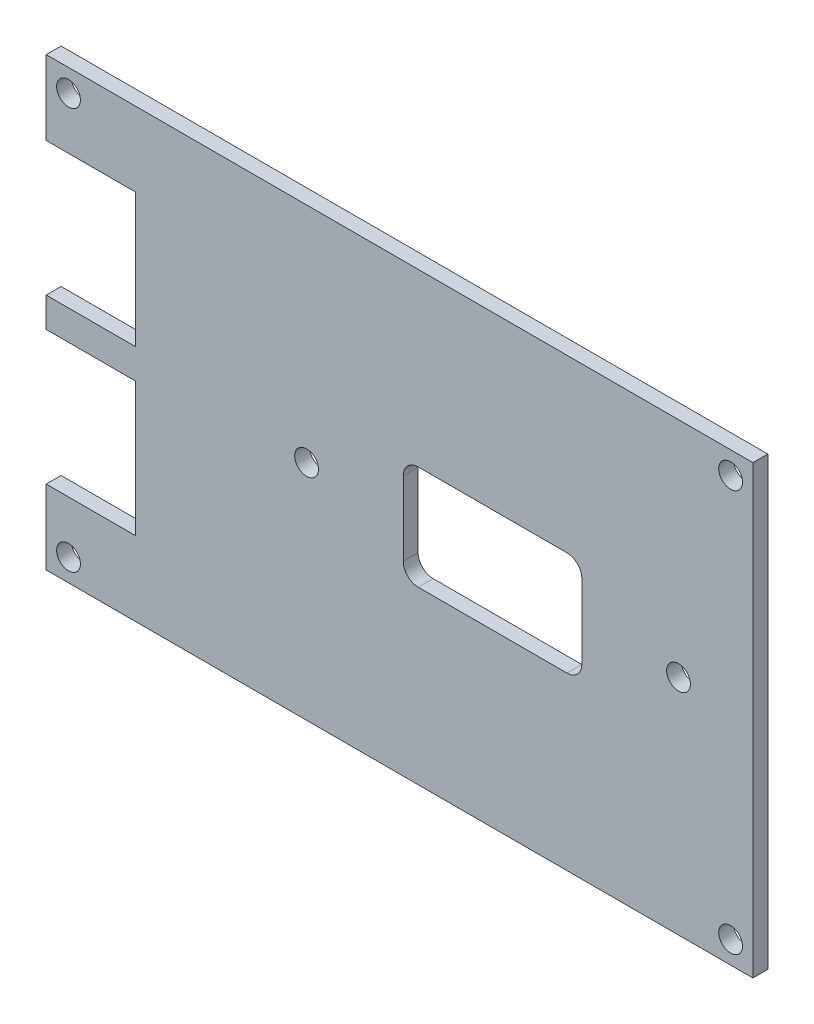
SolidWorks part; units mm, degrees
ref_plane "Front Plane" through (0, 0, 0) normal (0, 0, 1) x (1, 0, 0)
ref_plane "Top Plane" through (0, 0, 0) normal (0, 1, 0) x (1, 0, 0)
ref_plane "Right Plane" through (0, 0, 0) normal (1, 0, 0) x (0, 0, -1)
sketch "Sketch1" plane through (0, 0, 0) normal (0, 0, 1) x (1, 0, 0)
  line L0 (-4.5636, -11.1185) -> (20.4364, -11.1185) construction
  line L1 (-39.5636, 18.8815) -> (55.4364, 18.8815)
  line L2 (-39.5636, 18.8815) -> (-39.5636, 8.8815)
  line L3 (-39.5636, -41.1185) -> (55.4364, -41.1185)
  line L4 (55.4364, 18.8815) -> (55.4364, -41.1185)
  line L5 (20.4364, -4.1185) -> (20.4364, -11.1185) construction
  line L6 (10.4364, -4.1185) -> (30.4364, -4.1185)
  line L7 (8.4364, -6.1185) -> (8.4364, -16.1185)
  line L8 (10.4364, -18.1185) -> (30.4364, -18.1185)
  line L9 (32.4364, -6.1185) -> (32.4364, -16.1185)
  line L10 (20.4364, -18.1185) -> (20.4364, -11.1185) construction
  line L11 (20.4364, -11.1185) -> (45.4364, -11.1185) construction
  line L12 (-39.5636, -9.1185) -> (-39.5636, -13.1185)
  line L13 (-39.5636, 8.8815) -> (-27.5636, 8.8815)
  line L15 (-39.5636, -9.1185) -> (-27.5636, -9.1185)
  line L16 (-27.5636, 8.8815) -> (-27.5636, -9.1185)
  line L17 (-39.5636, -31.1185) -> (-39.5636, -41.1185)
  line L18 (-39.5636, -13.1185) -> (-27.5636, -13.1185)
  line L20 (-39.5636, -31.1185) -> (-27.5636, -31.1185)
  line L21 (-27.5636, -13.1185) -> (-27.5636, -31.1185)
  line L22 (-27.5636, 8.8815) -> (-27.5636, 18.8815) construction
  line L23 (-27.5636, -31.1185) -> (-27.5636, -41.1185) construction
  circle A0 centre (45.4364, -11.1185) radius 1.6
  circle A1 centre (-4.5636, -11.1185) radius 1.6
  circle A2 centre (-36.5636, 15.8815) radius 1.6
  circle A3 centre (52.4364, 15.8815) radius 1.6
  circle A4 centre (-36.5636, -38.1185) radius 1.6
  circle A5 centre (52.4364, -38.1185) radius 1.6
  arc A6 (10.4364, -4.1185) -> (8.4364, -6.1185) centre (10.4364, -6.1185) ccw
  arc A7 (32.4364, -6.1185) -> (30.4364, -4.1185) centre (30.4364, -6.1185) ccw
  arc A8 (10.4364, -18.1185) -> (8.4364, -16.1185) centre (10.4364, -16.1185) cw
  arc A9 (30.4364, -18.1185) -> (32.4364, -16.1185) centre (30.4364, -16.1185) ccw
  dimension "D3" = 50
  dimension "D6" = 2
  dimension "D7" = 2
  dimension "D8" = 2
  dimension "D9" = 2
  dimension "D1" = 60
  dimension "D2" = 95
  dimension "D4" = 10
  dimension "D5" = 30
  dimension "D10" = 20
  dimension "D11" = 10
  dimension "D12" = 3
  dimension "D13" = 3
  dimension "D14" = 3
  dimension "D15" = 3
  dimension "D16" = 3
  dimension "D17" = 3
  dimension "D18" = 3
  dimension "D19" = 3
  dimension "D20" = 54
  dimension "D21" = 12
  dimension "D22" = 18
  dimension "D23" = 10
extrude "Boss-Extrude1" add sketch "Sketch1" along normal blind 2
